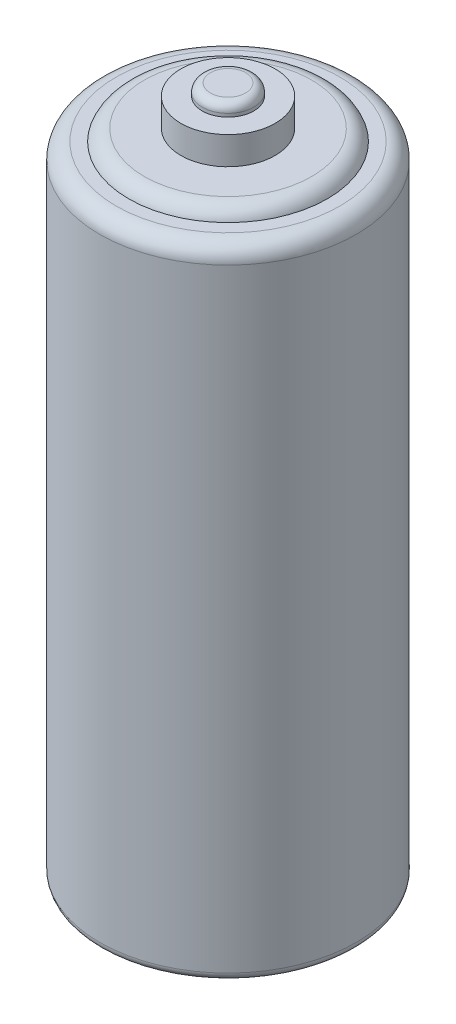
SolidWorks part; units mm, degrees
ref_plane "Front Plane" through (0, 0, 0) normal (0, 0, 1) x (1, 0, 0)
ref_plane "Top Plane" through (0, 0, 0) normal (0, 1, 0) x (1, 0, 0)
ref_plane "Right Plane" through (0, 0, 0) normal (1, 0, 0) x (0, 0, -1)
sketch "Sketch1" plane through (0, 0, 0) normal (0, 1, 0) x (1, 0, 0)
  circle A0 centre (-7.3675, 0.7702) radius 7.8223
extrude "Boss-Extrude1" add sketch "Sketch1" along normal blind 38.9
fillet "Fillet1" radius 1 1 edges at (-7.3675, 38.9, 7.0521)
sketch "Sketch2" plane through (0, 38.9, 0) normal (0, 1, 0) x (1, 0, 0)
  circle A0 centre (-7.3675, 0.7702) radius 6.624
  circle A1 centre (-7.3675, 0.7702) radius 6.8223 construction
sketch "Sketch7" plane through (0, 38.9, 0) normal (0, 1, 0) x (1, 0, 0)
  circle A0 centre (-7.3675, 0.7702) radius 6.0583
extrude "Boss-Extrude7" add sketch "Sketch7" along normal blind 0.7
fillet "Fillet5" radius 1 1 edges at (-7.3675, 39.6, 5.288)
sketch "Sketch8" plane through (0, 39.6, 0) normal (0, 1, 0) x (1, 0, 0)
  circle A0 centre (-7.3675, 0.7702) radius 2.8782
extrude "Boss-Extrude8" add sketch "Sketch8" along normal blind 1.7
sketch "Sketch9" plane through (0, 41.3, 0) normal (0, 1, 0) x (1, 0, 0)
  circle A0 centre (-7.3675, 0.7702) radius 1.5735
extrude "Boss-Extrude9" add sketch "Sketch9" along normal blind 0.7
fillet "Fillet7" radius 0.5 1 edges at (-7.3675, 42, 0.8032)
sketch "Sketch10" plane through (0, 0, 0) normal (0, -1, 0) x (1, 0, 0)
  circle A0 centre (-7.3675, -0.7702) radius 6.6156
  circle A1 centre (-7.3675, -0.7702) radius 7.8223 construction
extrude "Boss-Extrude11" add sketch "Sketch10" along normal blind 0.2
fillet "Fillet8" radius 0.5 1 edges at (-7.3675, 0, 7.0521)
fillet "Fillet9" radius 0.5 1 edges at (-7.3675, -0.2, -7.3858)
sketch "Sketch11" plane through (0, -0.2, 0) normal (0, -1, 0) x (1, 0, 0)
  circle A0 centre (-7.3675, -0.7702) radius 5.4035
extrude "Boss-Extrude12" add sketch "Sketch11" along normal blind 0.2
fillet "Fillet10" radius 0.5 1 edges at (-7.3675, -0.4, -6.1738)
